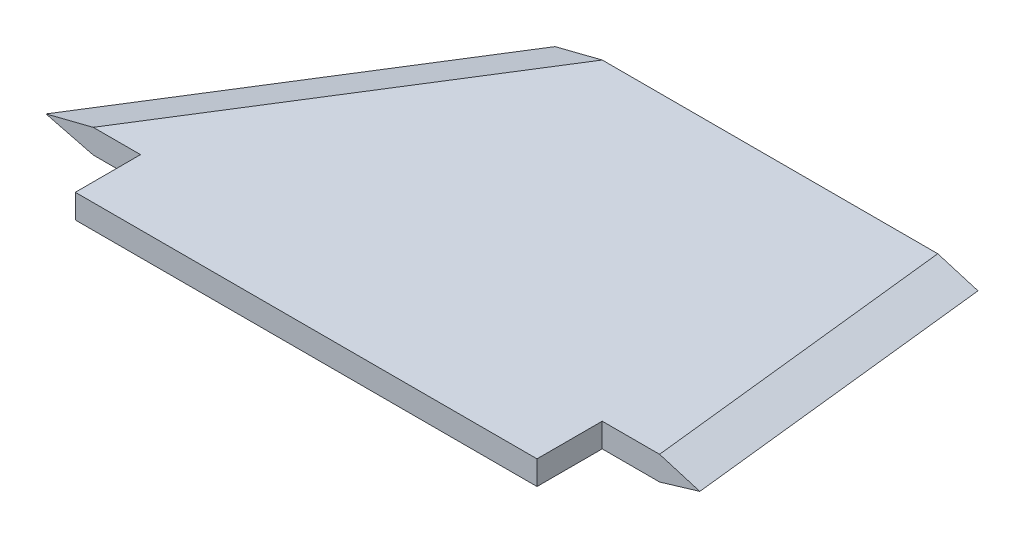
SolidWorks part; units mm, degrees
ref_plane "Front Plane" through (0, 0, 0) normal (0, 0, 1) x (1, 0, 0)
ref_plane "Top Plane" through (0, 0, 0) normal (0, 1, 0) x (1, 0, 0)
ref_plane "Right Plane" through (0, 0, 0) normal (1, 0, 0) x (0, 0, -1)
sketch "Sketch1" plane through (0, 0, 0) normal (0, 1, 0) x (1, 0, 0)
  line L0 (0, 0) -> (152.4, 0)
  line L1 (152.4, 0) -> (144.78, 68.834)
  line L2 (144.78, 68.834) -> (43.18, 68.834)
  line L3 (43.18, 68.834) -> (0, 0)
  dimension "D1" = 152.4
  dimension "D2" = 101.6
  dimension "D3" = 43.18
  dimension "D4" = 68.834
extrude "Boss-Extrude1" add sketch "Sketch1" along normal blind 5.2832
sketch "Sketch2" plane through (0, 0, 0) normal (0, 1, 0) x (1, 0, 0)
  line L0 (25.4, 0) -> (25.4, -14.351)
  line L1 (0, 0) -> (152.4, 0) construction
  line L2 (25.4, -14.351) -> (127, -14.351)
  line L3 (127, -14.351) -> (127, 0)
  line L8 (43.18, 68.834) -> (0, 0)
  line L9 (0, 0) -> (152.4, 0)
  line L10 (152.4, 0) -> (144.78, 68.834)
  line L11 (144.78, 68.834) -> (43.18, 68.834)
  line L13 (25.4, 0) -> (127, 0)
  dimension "D1" = 101.6
  dimension "D2" = 14.351
  dimension "D3" = 14.351
  dimension "D4" = 25.4
  dimension "D5" = 25.4
  dimension "D6" = 0
extrude "Boss-Extrude2" add sketch "Sketch2" along normal blind 5.2832
chamfer "Chamfer1" distance 3.81 distance2 12.7 2 edges at (21.59, 0, -34.417) (21.59, 5.2832, -34.417) first distance on face at (21.59, 2.6416, -34.417)
chamfer "Chamfer2" distance 12.7 distance2 3.81 1 edges at (148.59, 0, -34.417) first distance on face at (84.393, 0, -13.6207)
chamfer "Chamfer3" distance 3.81 distance2 12.7 1 edges at (148.59, 5.2832, -34.417) first distance on face at (148.59, 4.5466, -34.417)
